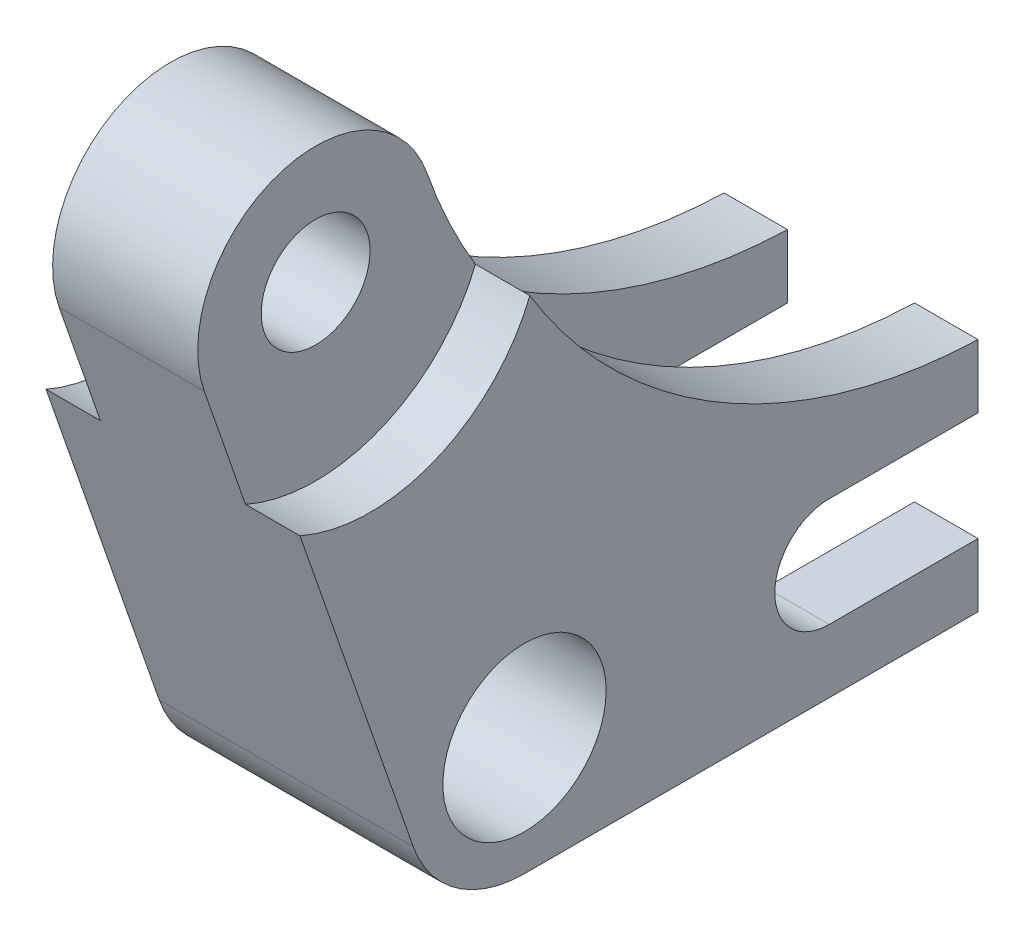
SolidWorks part; units mm, degrees
material "Ouro puro"
ref_plane "Plano frontal" through (0, 0, 0) normal (0, 0, 1) x (1, 0, 0)
ref_plane "Plano superior" through (0, 0, 0) normal (0, 1, 0) x (1, 0, 0)
ref_plane "Plano direito" through (0, 0, 0) normal (1, 0, 0) x (0, 0, -1)
sketch "Esboço1" plane through (0, 0, 0) normal (1, 0, 0) x (0, 0, -1)
  line L0 (0, 0) -> (-17.0334, 49) construction
  line L1 (0, -13) -> (50, -13)
  line L2 (-12.2792, -4.2685) -> (-29.3126, 44.7315)
  line L4 (50, -13) -> (50, 13)
  arc A0 (-12.2792, -4.2685) -> (0, -13) centre (0, 0) ccw
  arc A1 (-4.7541, 53.2685) -> (-29.3126, 44.7315) centre (-17.0334, 49) ccw
  circle A2 centre (-17.0334, 49) radius 6
  circle A3 centre (0, 0) radius 9
  arc A4 (-4.7541, 53.2685) -> (50, 13) centre (51.9193, 72.9693) ccw
  point P1 (-8.5167, 24.5)
  dimension "D1" = 13
  dimension "D2" = 12
  dimension "D3" = 18
  dimension "D6" = 60
  dimension "D4" = 50
  dimension "D5" = 26
  dimension "D7" = 62
extrude "Ressalto-extrusão1" add sketch "Esboço1" along normal blind 28
sketch "Esboço2" plane through (0, 0, 0) normal (1, 0, 0) x (0, 0, -1)
  line L0 (50, 0) -> (33.5996, 0) construction
  line L1 (50, -13) -> (50, 13) construction
  line L2 (50, -6) -> (33.5996, -6)
  line L3 (50, 6) -> (33.5996, 6)
  arc A0 (50, -6) -> (50, 6) centre (50, 0) ccw
  arc A1 (33.5996, 6) -> (33.5996, -6) centre (33.5996, 0) ccw
  point P4 (41.7998, 0)
  dimension "D2" = 6
  dimension "D1" = 7
extrude "Corte-extrusão1" cut sketch "Esboço2" along normal through all
sketch "Esboço3" plane through (0, 0, 0) normal (0, 1, 0) x (1, 0, 0)
  line L0 (28, 50) -> (0, 50) construction
  line L1 (7, 50) -> (21, 50)
  line L2 (7, 50) -> (7, 12)
  line L3 (7, 12) -> (21, 12)
  line L4 (21, 50) -> (21, 12)
  dimension "D1" = 14
  dimension "D2" = 38
  dimension "D3" = 7
extrude "Corte-extrusão3" cut sketch "Esboço3" against normal through all and the other way through all
sketch "Esboço4" plane through (0, 0, 0) normal (1, 0, 0) x (0, 0, -1)
  line L0 (-17.0334, 49) -> (-21.3019, 61.2792) construction
  line L1 (-34.9799, 42.7614) -> (-39.2484, 55.0407)
  line L2 (0.9132, 55.2386) -> (-3.3553, 67.5178)
  arc A0 (-4.7541, 53.2685) -> (-29.3126, 44.7315) centre (-17.0334, 49) ccw construction
  arc A1 (-34.9799, 42.7614) -> (0.9132, 55.2386) centre (-17.0334, 49) ccw
  arc A2 (-3.3553, 67.5178) -> (-39.2484, 55.0407) centre (-21.3019, 61.2792) ccw
  point P6 (-19.1676, 55.1396)
  dimension "D1" = 19
extrude "Corte-extrusão4" cut sketch "Esboço4" along normal blind 6
extrude "Corte-extrusão5" cut sketch "Esboço4<2>" against normal blind 6 from surface starting at face at (28, 49, 11.0334)
sketch "Esboço4<2>" plane through (0, 0, 0) normal (1, 0, 0) x (0, 0, -1) same geometry as "Esboço4"
